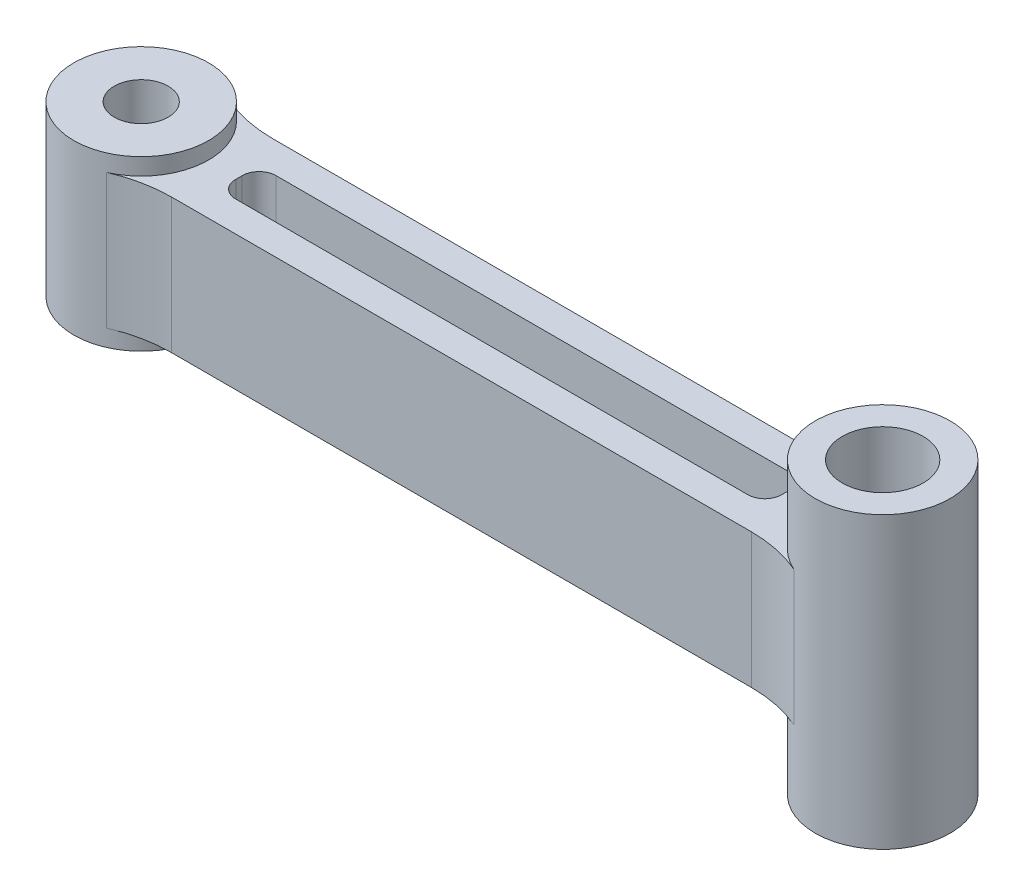
SolidWorks part; units mm, degrees
note: The reader was unsure of these and kept them because the rebuilt part matched: shared geometry of "Sketch2<3>".
ref_plane "Front Plane" through (0, 0, 0) normal (0, 0, 1) x (1, 0, 0)
ref_plane "Top Plane" through (0, 0, 0) normal (0, 1, 0) x (1, 0, 0)
ref_plane "Right Plane" through (0, 0, 0) normal (1, 0, 0) x (0, 0, -1)
sketch "Sketch2" plane through (0, 0, 0) normal (0, 1, 0) x (1, 0, 0)
  line L0 (0, 7.5) -> (-45, 7.5) construction
  line L1 (0, 0) -> (-48.3856, 0)
  line L2 (0, 0) -> (0, 15)
  line L3 (0, 15) -> (-48.3856, 15)
  circle A0 centre (-55, 7.5) radius 10
  circle A1 centre (-55, 7.5) radius 6
  dimension "D1" = 20
  dimension "D2" = 12
  dimension "D3" = 15
  dimension "D4" = 55
extrude "Boss-Extrude1" add sketch "Sketch2" along normal mid plane 43 contours A0 A1
extrude "Boss-Extrude2" add sketch "Sketch2<3>" along normal mid plane 20 contours L2 L0 A0 L1 | L0 L2 L3 A0
sketch "Sketch2<3>" plane through (0, 0, 0) normal (0, 1, 0) x (1, 0, 0) same geometry as "Sketch2"
mirror "Mirror1" about plane through (0, 10, 0) normal (-1, 0, 0) of bodies 102
sketch "Sketch3" plane through (0, 10, 0) normal (0, 1, 0) x (1, 0, 0)
  line L11 (48.3856, 10.5) -> (-48.3856, 10.5)
  line L12 (40.8137, 10.5) -> (-40.8137, 10.5)
  line L14 (48.3856, 4.5) -> (-48.3856, 4.5)
  line L15 (40.8137, 4.5) -> (-40.8137, 4.5)
  arc A4 (-45.4092, -3.375) -> (-45.4092, 18.375) centre (-55, 7.5) ccw
  arc A5 (-40.8137, 4.5) -> (-40.8137, 10.5) centre (-55, 7.5) ccw
  arc A7 (45.4092, 18.375) -> (45.4092, -3.375) centre (55, 7.5) ccw
  arc A8 (40.8137, 10.5) -> (40.8137, 4.5) centre (55, 7.5) ccw
  dimension "D1" = 4.5
  dimension "D2" = 4.5
  dimension "D3" = 4.5
  dimension "D4" = 4.5
extrude "Cut-Extrude1" cut sketch "Sketch3" against normal blind 6.25
mirror "Mirror2" about plane through (0, 0, 0) normal (0, 1, 0) of "Cut-Extrude1"
fillet "Fillet1" radius 20 4 edges at (48.3856, 0, -15) (48.3856, 0, 0) (-48.3856, 0, -15) (-48.3856, 0, 0)
fillet "Fillet2" radius 2.5 8 edges at (-40.8137, -6.875, -4.5) (-40.8137, -6.875, -10.5) (40.8137, -6.875, -4.5) (40.8137, -6.875, -10.5) (40.8137, 6.875, -10.5) (40.8137, 6.875, -4.5) (-40.8137, 6.875, -4.5) (-40.8137, 6.875, -10.5)
other "Move Face1" flip direction yes face at (-55, 21.5, -1.5) parameters "D1"=9
other "Move Face2" flip direction yes face at (-55, -21.5, -1.5) parameters "D1"=9
other "Move Face3" face at (-55, 12.5, -1.5) parameters "D1"=2
